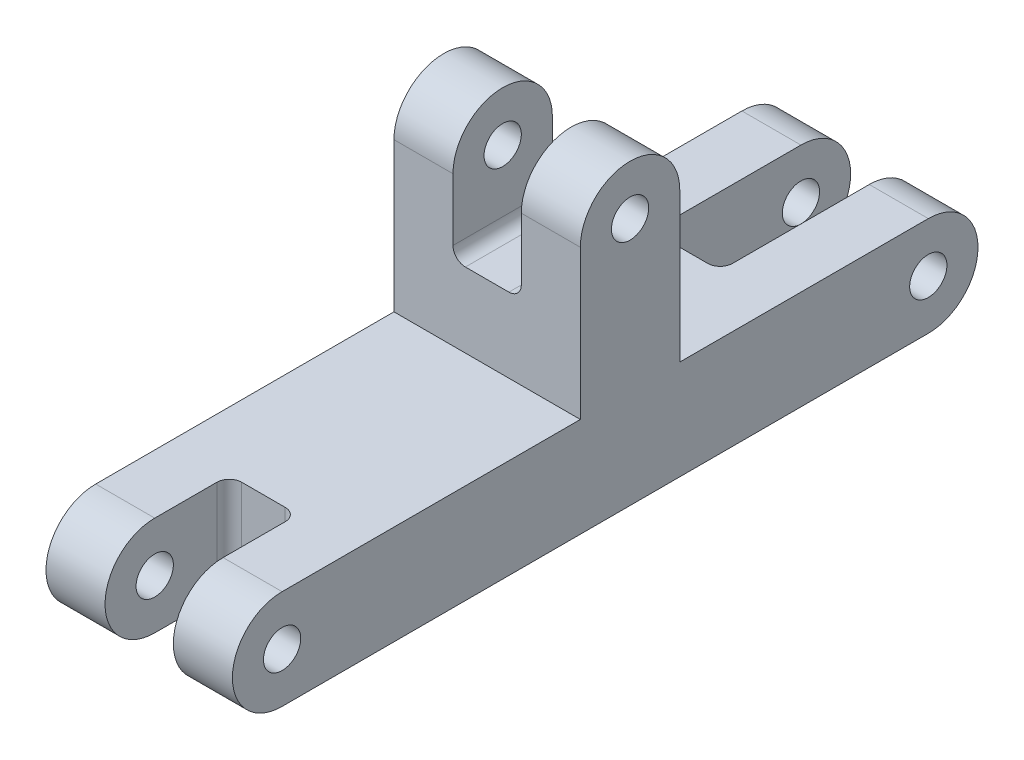
SolidWorks part; units mm, degrees
ref_plane "Alzado" through (0, 0, 0) normal (0, 0, 1) x (1, 0, 0)
ref_plane "Planta" through (0, 0, 0) normal (0, 1, 0) x (1, 0, 0)
ref_plane "Vista lateral" through (0, 0, 0) normal (1, 0, 0) x (0, 0, -1)
sketch "Croquis1" plane through (0, 0, 0) normal (1, 0, 0) x (0, 0, -1)
  line L0 (-10, 0) -> (10, 0) construction
  line L1 (-10, 4) -> (-18, 4) construction
  line L2 (-10, -4) -> (10, -4)
  line L3 (-10, 4) -> (10, 4)
  line L5 (-18, 4) -> (-18, 16)
  line L6 (-18, 16) -> (-10, 16) construction
  line L7 (-10, 4) -> (-10, 16)
  line L8 (-18, 4) -> (-42, 4)
  line L9 (-10, -4) -> (-42, -4)
  line L10 (-42, 4) -> (-42, -4) construction
  arc A0 (-10, 4) -> (-10, -4) centre (-10, 0) ccw construction
  arc A1 (10, -4) -> (10, 4) centre (10, 0) ccw
  circle A2 centre (10, 0) radius 1.5
  arc A3 (-10, 16) -> (-18, 16) centre (-14, 16) ccw
  circle A4 centre (-14, 16) radius 1.5
  circle A5 centre (-10, 0) radius 1.5 construction
  arc A6 (-42, 4) -> (-42, -4) centre (-42, 0) ccw
  circle A7 centre (-42, 0) radius 1.5
  point P3 (0, 0)
  dimension "D2" = 4
  dimension "D3" = 3
  dimension "D4" = 4
  dimension "D7" = 24
  dimension "D1" = 20
  dimension "D6" = 12
extrude "Saliente-Extruir1" add sketch "Croquis1" along normal mid plane 15
sketch "Croquis2" plane through (0, 0, 0) normal (1, 0, 0) x (0, 0, -1)
  line L0 (-18, 16) -> (-18, 4) construction
  line L1 (-18, 10) -> (-10, 10)
  line L2 (-18, 10) -> (-18, 20)
  line L3 (-18, 20) -> (-10, 20)
  line L4 (-10, 10) -> (-10, 20)
  line L5 (-10, 4) -> (-10, 16) construction
  line L11 (-42, -4) -> (10, -4) construction
  line L12 (10, 4) -> (-10, 4) construction
  line L13 (-2, 4) -> (14, 4)
  line L14 (-2, 4) -> (-2, -4)
  line L15 (-2, -4) -> (14, -4)
  line L16 (14, 4) -> (14, -4)
  line L18 (-36, 4) -> (-46, 4)
  line L19 (-36, 4) -> (-36, -4)
  line L20 (-36, -4) -> (-46, -4)
  line L21 (-46, 4) -> (-46, -4)
  line L22 (-42, -4) -> (10, -4) construction
  line L23 (-18, 4) -> (-42, 4) construction
  arc A0 (-10, 16) -> (-18, 16) centre (-14, 16) ccw construction
  arc A2 (10, -4) -> (10, 4) centre (10, 0) ccw construction
  arc A5 (-42, 4) -> (-42, -4) centre (-42, 0) ccw construction
  dimension "D5" = 10
  dimension "D1" = 10
  dimension "D3" = 16
extrude "Cortar-Extruir1" cut sketch "Croquis2" against normal mid plane 5.5
fillet "Redondeo1" radius 1 6 edges at (2.75, 0, 36) (-2.75, 0, 36) (2.75, 0, 2) (-2.75, 0, 2) (2.75, 10, 14) (-2.75, 10, 14)
